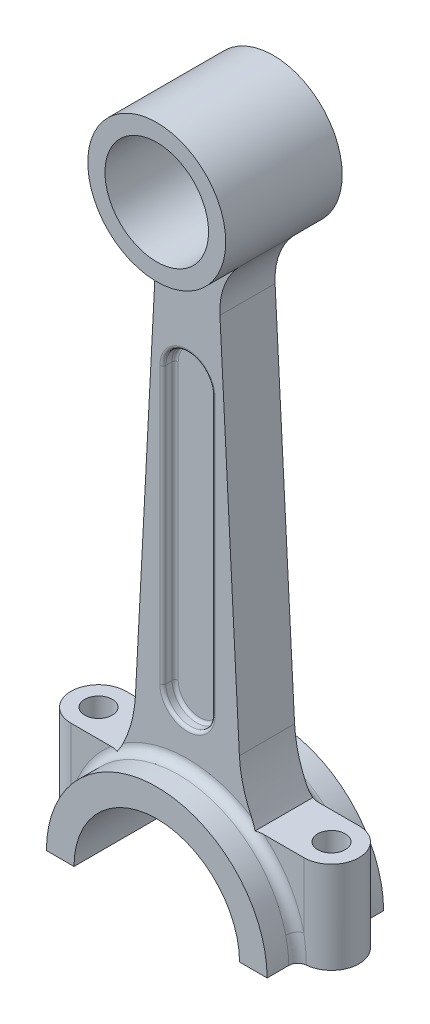
SolidWorks part; units mm, degrees
ref_plane "Front Plane" through (0, 0, 0) normal (0, 0, 1) x (1, 0, 0)
ref_plane "Top Plane" through (0, 0, 0) normal (0, 1, 0) x (1, 0, 0)
ref_plane "Right Plane" through (0, 0, 0) normal (1, 0, 0) x (0, 0, -1)
sketch "Sketch1" plane through (0, 0, 0) normal (0, 0, 1) x (1, 0, 0)
  line L0 (0, 0) -> (0, -201.2) construction
  line L1 (-10, -20.1556) -> (-17.8497, -169.9368)
  line L2 (10, -20.1556) -> (17.8497, -169.9368)
  circle A0 centre (0, 0) radius 22.5
  circle A1 centre (0, 0) radius 16.9
  circle A2 centre (0, -201.2) radius 36
  circle A3 centre (0, -201.2) radius 27
  dimension "D1" = 45
  dimension "D2" = 33.8
  dimension "D3" = 72
  dimension "D4" = 54
  dimension "D5" = 201.2
  dimension "D6" = 20
  dimension "D7" = 6
extrude "Boss-Extrude1" add sketch "Sketch1" along normal mid plane 38 contours A1 A0 | A2 A3 region at (-11.5231, 18.5805, 0) region at (0, -166.2182, 0)
sketch "Sketch9" plane through (0, 0, 0) normal (0, 0, 1) x (1, 0, 0)
  line L0 (0, 0) -> (0, -201.2) construction
  line L1 (-10, -20.1556) -> (-17.8497, -169.9368)
  line L2 (10, -20.1556) -> (17.8497, -169.9368)
  circle A0 centre (0, -201.2) radius 36 construction
  circle A1 centre (0, 0) radius 22.5 construction
  arc A2 (-10, -20.1556) -> (10, -20.1556) centre (0, 0) ccw
  arc A3 (-17.8497, -169.9368) -> (17.8497, -169.9368) centre (0, -201.2) cw
  dimension "D1" = 6
  dimension "D2" = 20
extrude "Boss-Extrude3" add sketch "Sketch9" along normal mid plane 18
sketch "Sketch3" plane through (0, 0, 19) normal (0, 0, 1) x (1, 0, 0)
  line L0 (-36, -201.2) -> (-27, -201.2)
  line L1 (27, -201.2) -> (36, -201.2)
  circle A0 centre (0, -201.2) radius 36 construction
  arc A1 (-36, -201.2) -> (36, -201.2) centre (0, -201.2) ccw
  arc A2 (-27, -201.2) -> (27, -201.2) centre (0, -201.2) ccw
  circle A3 centre (0, -201.2) radius 27 construction
extrude "Cut-Extrude3" cut sketch "Sketch3" against normal through all both and the other way through all
ref_plane "Plane1" through (0, -171.2, 0) normal (0, -1, 0) x (-1, 0, 0)
fillet "Fillet7" radius 40 2 edges at (17.8497, -169.9368, 0) (-17.8497, -169.9368, 0)
fillet "Fillet8" radius 22.5 2 edges at (-10, -20.1556, 0) (10, -20.1556, 0)
sketch "Sketch4" plane through (0, -171.2, 0) normal (0, -1, 0) x (-1, 0, 0)
  line L0 (-38, 0) -> (38, 0) construction
  line L1 (-38, 9) -> (38, 9)
  line L2 (-38, -9) -> (38, -9)
  arc A0 (-38, 9) -> (-38, -9) centre (-38, 0) ccw
  arc A1 (38, -9) -> (38, 9) centre (38, 0) ccw
  point P2 (0, 0)
  dimension "D2" = 9
  dimension "D1" = 76
extrude "Boss-Extrude2" add sketch "Sketch4" along normal up to surface (30 mm away) up to face at (31.5, -201.2, 0)
sketch "Sketch7" plane through (0, 0, -9) normal (0, 0, -1) x (-1, 0, 0)
  line L0 (-27, -201.2) -> (27, -201.2)
  arc A0 (-27, -201.2) -> (27, -201.2) centre (0, -201.2) cw
  arc A1 (27, -201.2) -> (-27, -201.2) centre (0, -201.2) ccw construction
extrude "Cut-Extrude4" cut sketch "Sketch7" against normal through all both and the other way through all
sketch "Sketch8" plane through (0, -171.2, 0) normal (0, 1, 0) x (1, 0, 0)
  circle A0 centre (-38, 0) radius 4.5
  circle A1 centre (38, 0) radius 4.5
  dimension "D1" = 9
extrude "Cut-Extrude5" cut sketch "Sketch8" against normal up to next
sketch "Sketch10" plane through (0, 0, 9) normal (0, 0, 1) x (1, 0, 0)
  line L0 (0, 0) -> (0, -201.2) construction
  line L1 (0, -145.6) -> (0, -55.6) construction
  line L2 (-8, -145.6) -> (-8, -55.6)
  line L3 (8, -145.6) -> (8, -55.6)
  arc A0 (-8, -145.6) -> (8, -145.6) centre (0, -145.6) ccw
  arc A1 (8, -55.6) -> (-8, -55.6) centre (0, -55.6) ccw
  point P6 (0, -100.6)
  dimension "D2" = 8
  dimension "D1" = 90
extrude "Cut-Extrude8" cut sketch "Sketch10" against normal blind 4
fillet "Fillet6" radius 1 8 edges at (0, -47.6, 9) (8, -100.6, 9) (0, -153.6, 9) (0, -47.6, 5) (8, -100.6, 5) (0, -153.6, 5) (-8, -100.6, 5) (-8, -100.6, 9)
mirror "Mirror3" about plane through (0, 0, 0) normal (0, 0, 1) of "Fillet6", "Cut-Extrude8"
fillet "Fillet9" radius 3 2 edges at (0, -165.2, 9) (0, -165.2, -9)
